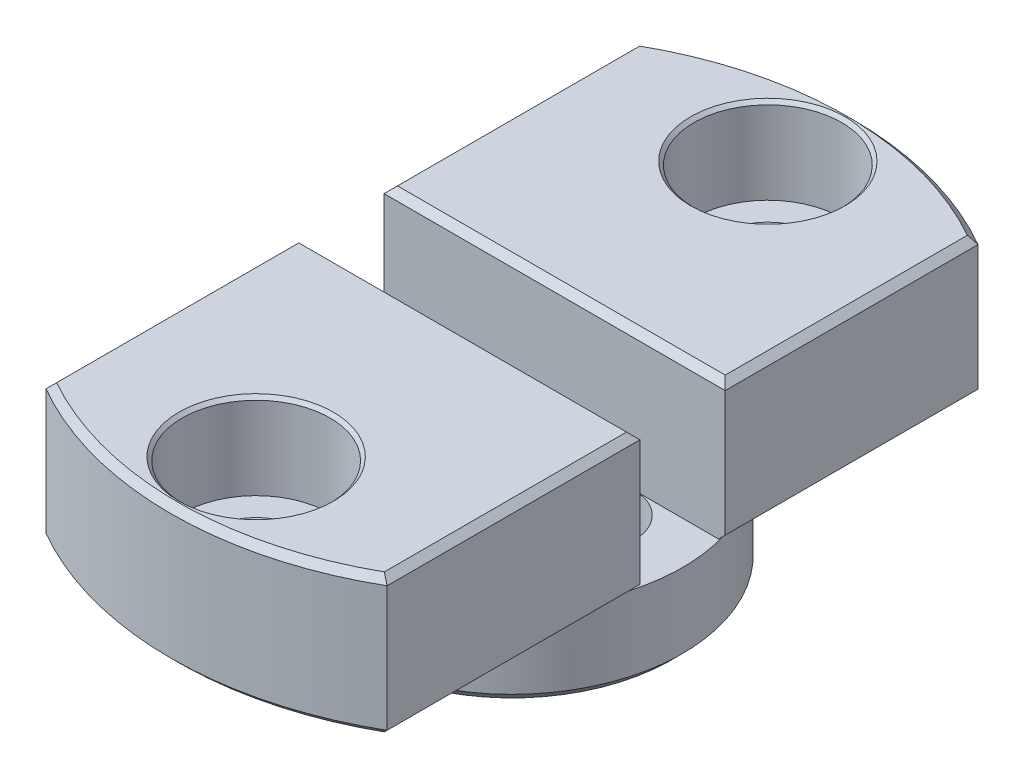
SolidWorks part; units mm, degrees
material "AISI Type A2 Tool Steel"
ref_plane "Front Plane" through (0, 0, 0) normal (0, 0, 1) x (1, 0, 0)
ref_plane "Top Plane" through (0, 0, 0) normal (0, 1, 0) x (1, 0, 0)
ref_plane "Right Plane" through (0, 0, 0) normal (1, 0, 0) x (0, 0, -1)
sketch "Sketch1" plane through (0, 0, 0) normal (0, 1, 0) x (1, 0, 0)
  line L0 (0, 25.4) -> (0, -25.4) construction
  line L1 (-12.7, 21.997) -> (-12.7, -21.997)
  line L2 (12.7, 21.997) -> (12.7, -21.997)
  arc A0 (-12.7, -21.997) -> (12.7, -21.997) centre (0, 0) ccw
  arc A1 (12.7, 21.997) -> (-12.7, 21.997) centre (0, 0) ccw
  dimension "D1" = 50.8
  dimension "D2" = 25.4
extrude "Boss-Extrude1" add sketch "Sketch1" against normal blind 10.32
sketch "Sketch2" plane through (0, -10.32, 0) normal (0, -1, 0) x (1, 0, 0)
  circle A0 centre (0, 0) radius 12.7
  dimension "D1" = 25.4
extrude "Boss-Extrude2" add sketch "Sketch2" along normal blind 6.35
sketch "Sketch9" plane through (0, 0, 0) normal (0, 0, 1) x (1, 0, 0)
  line L1 (-12.7, -16.67) -> (12.7, -16.67) construction
  line L2 (0, -9.1685) -> (0, 9.1685) construction
  circle A0 centre (1.2, -13.495) radius 1.2
  dimension "D1" = 2.4
  dimension "D2" = 3.175
  dimension "D3" = 1.2
extrude "Cut-Extrude3" cut sketch "Sketch9" against normal through all both and the other way through all
sketch "Sketch10" plane through (0, 0, 0) normal (0, 0, 1) x (1, 0, 0)
  line L0 (9.1281, -16.67) -> (9.1281, -10.32)
  line L1 (-12.7, -16.67) -> (12.7, -16.67) construction
  line L2 (-12.7, -10.32) -> (12.7, -10.32) construction
  line L3 (9.1281, -10.32) -> (12.7, -10.32)
  line L4 (12.7, -10.32) -> (12.7, 0)
  line L5 (13.97, 0) -> (-13.97, 0) construction
  line L6 (12.7, -10.32) -> (12.7, 0) construction
  line L7 (12.7, 0) -> (-12.7, 0)
  line L8 (-12.7, 0) -> (-12.7, -10.32)
  line L9 (-12.7, -10.32) -> (-10.3263, -10.32)
  line L10 (-10.3263, -10.32) -> (-6.2025, -16.67)
  line L11 (-6.2025, -16.67) -> (9.1281, -16.67)
  line L12 (1.2, -13.495) -> (-0.8619, -10.32) construction
  line L13 (-12.7, -10.32) -> (12.7, -10.32) construction
  line L14 (0, -9.1685) -> (0, 9.1685) construction
  dimension "D1" = 7.9375
  dimension "D2" = 33
  dimension "D3" = 9.1281
extrude "Cut-Extrude4" cut sketch "Sketch10" against normal mid plane 6.35
sketch "Sketch12" plane through (0, 0, 0) normal (0, 1, 0) x (1, 0, 0)
  line L0 (-14.9361, 0) -> (15.4723, 0) construction
  line L2 (0, 19.05) -> (0, -19.05) construction
  point P0 (0, 19.05)
  point P2 (0, -19.05)
  dimension "D1" = 38.1
hole_wizard "CBORE for M6 Hex Socket Head Cap Screw2" positions "Sketch12" profile "Sketch13" counterbore size "M6" standard "ISO" end condition up to next
sketch "Sketch13" plane through (0, 0, -19.05) normal (1, 0, 0) x (0, 0, 1)
  line L0 (0, 0) -> (0, 10.32)
  line L1 (3.3, 10.12) -> (3.5, 10.32)
  line L2 (3.3, 10.12) -> (3.3, 6.6)
  line L3 (3.3, 6.6) -> (3.5, 6.4)
  line L4 (3.5, 6.4) -> (5.5, 6.4)
  line L5 (5.5, 6.4) -> (5.5, 0.25)
  line L6 (5.5, 0.25) -> (5.75, 0)
  line L7 (5.75, 0) -> (0, 0)
  line L8 (-5.5, 0.25) -> (-5.75, 0) construction
  line L9 (-3.3, 6.6) -> (-3.5, 6.4) construction
  line L11 (0, -6.35) -> (0, 107.95) construction
  line L12 (3.5, 10.32) -> (0, 10.32)
  line L13 (-3.3, 10.12) -> (-3.5, 10.32) construction
  dimension "Thru Hole Dia." = 6.6
  dimension "Thru Hole Depth" = 10.32
  dimension "C'Bore Dia." = 11
  dimension "C'Bore Depth" = 6.4
  dimension "Near C'Sink Dia." = 11.5
  dimension "Near C'Sink Angle" = 90
  dimension "Mid C'Sink Dia." = 7
  dimension "Mid C'Sink Angle" = 90
  dimension "Far C'Sink Dia." = 7
  dimension "Far C'Sink Angle" = 90
fillet "Fillet2" radius 3.175 4 edges at (9.1281, -13.495, 3.175) (9.1281, -16.67, 0) (9.1281, -13.495, -3.175) (9.1281, -10.32, 0)
fillet "Fillet3" radius 3.175 4 edges at (-10.3263, -10.32, 0) (-8.2644, -13.495, 3.175) (-8.2644, -13.495, -3.175) (-6.2025, -16.67, 0)
sketch "Sketch14" plane through (0, 0, 0) normal (0, 0, 1) x (1, 0, 0)
  line L0 (1.2, -13.495) -> (-5.4569, -17.8181) construction
  line L1 (-10.3263, -10.32) -> (-6.2025, -16.67) construction
  line L2 (-8.4851, -13.1551) -> (-13.4266, -16.3641) construction
  line L4 (-2.9847, -12.4447) -> (-7.9814, -15.6896)
  line L5 (-7.9814, -15.6896) -> (-10.498, -14.4622)
  line L6 (-10.498, -14.4622) -> (-4.2918, -10.4319)
  line L7 (-4.2918, -10.4319) -> (-2.9847, -12.4447)
  dimension "D1" = 5.56
  dimension "D2" = 59
  dimension "D3" = 2.4
  dimension "D4" = 4.8
  dimension "D5" = 5
revolve "Cut-Revolve5" cut sketch "Sketch14" angle 360 about L2
chamfer "Chamfer2" distance 0.8 angle 45 1 edges at (0, -16.67, -12.7)
chamfer "Chamfer3" distance 0.5 angle 45 14 edges at (0, 0, -25.4) (12.7, 0, -12.586) (-12.7, 0, -12.586) (0, 0, -3.175) (-12.7, 0, 12.586) (0, 0, 3.175) (12.7, 0, 12.586) (0, 0, 25.4) (12.7, -10.32, -12.586) (0, -10.32, -25.4) (-12.7, -10.32, -12.586) (-12.7, -10.32, 12.586) (12.7, -10.32, 12.586) (0, -10.32, 25.4)
